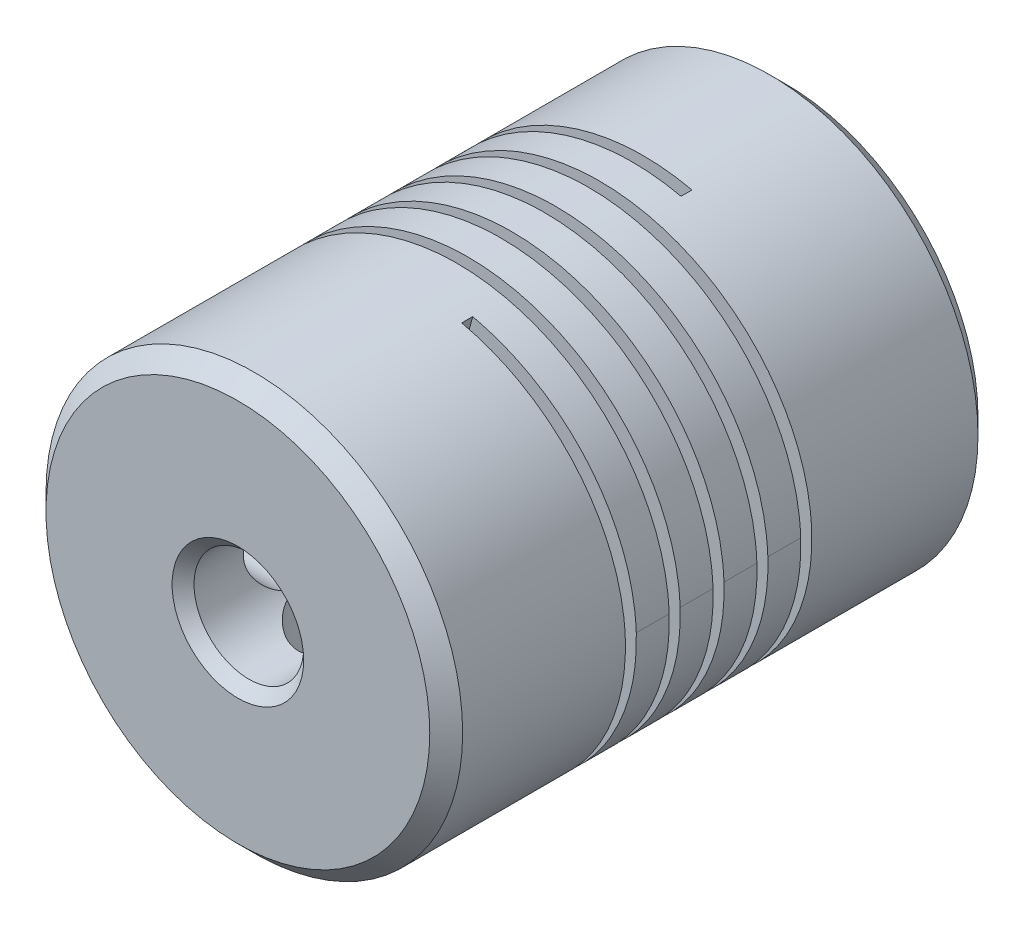
SolidWorks part; units mm, degrees
material "6063-T5"
ref_plane "Спереди" through (0, 0, 0) normal (0, 0, 1) x (1, 0, 0)
ref_plane "Сверху" through (0, 0, 0) normal (0, 1, 0) x (1, 0, 0)
ref_plane "Справа" through (0, 0, 0) normal (1, 0, 0) x (0, 0, -1)
sketch "Эскиз1" plane through (0, 0, 0) normal (0, 0, 1) x (1, 0, 0)
  circle A0 centre (0, 0) radius 9.5
  dimension "D1" = 19
extrude "Body" add sketch "Эскиз1" along normal blind 25
sketch "Эскиз2" plane through (0, 0, 25) normal (0, 0, 1) x (1, 0, 0)
  circle A0 centre (0, 0) radius 2.5
  dimension "D1" = 5
extrude "RodHole" cut sketch "Эскиз2" against normal blind 42
chamfer "Фаска1" distance 0.75 angle 45 2 edges at (9.5, 0, 25) (9.5, 0, 0)
chamfer "Фаска2" distance 0.5 angle 45 2 edges at (2.5, 0, 25) (2.5, 0, 0)
sketch "Эскиз3" plane through (0, 0, 0) normal (1, 0, 0) x (0, 0, -1)
  circle A0 centre (-4.5, 0) radius 1.75
  circle A1 centre (-20.5, 0) radius 1.75
  dimension "D1" = 3.5
  dimension "D2" = 3.5
  dimension "D3" = 4.5
  dimension "D4" = 20.5
extrude "SetScrewHoles1" cut sketch "Эскиз3" against normal blind 12
cosmetic thread "Условное изображение резьбы1" parameters "D2"=4
cosmetic thread "Условное изображение резьбы2" parameters "D2"=4
sketch "Эскиз4" plane through (0, 0, 0) normal (0, 1, 0) x (1, 0, 0)
  circle A0 centre (0, -4.5) radius 1.75
  circle A1 centre (0, -20.5) radius 1.75
  dimension "D1" = 3.5
  dimension "D2" = 3.5
  dimension "D3" = 4.5
  dimension "D4" = 20.5
extrude "SetScrewHoles2" cut sketch "Эскиз4" against normal blind 12
cosmetic thread "Условное изображение резьбы3" parameters "D2"=4
cosmetic thread "Условное изображение резьбы4" parameters "D2"=4
ref_plane "Плоскость1" through (0, 0, 17) normal (0, 0, 1) x (1, 0, 0)
sketch "Эскиз6" plane through (0, 0, 17) normal (0, 0, 1) x (1, 0, 0)
  circle A0 centre (0, 0) radius 9.5
curve "Спираль1" pitch 2 height 10 radius 9.5 centre (0, 0, 17) axis (0, 0, -1) start towards (0.2588, 0.9659, 0)
ref_plane "Плоскость2" through (0, 0, 0) normal (0.9659, -0.2588, 0) x (0, 0, -1)
sketch "Эскиз7" plane through (0, 0, 0) normal (0.9659, -0.2588, 0) x (0, 0, -1)
  line L0 (-0.75, 9.5) -> (-24.25, 9.5) construction
  line L1 (-6.75, 10.0798) -> (-7.25, 10.0798)
  line L2 (-6.75, 10.0798) -> (-6.75, 1.4319)
  line L3 (-6.75, 1.4319) -> (-7.25, 1.4319)
  line L4 (-7.25, 10.0798) -> (-7.25, 1.4319)
  spline S0 degree 3 poles (-17, 9.5) (-16.9586, 9.5) (-16.8749, 9.0054) (-16.75, 6.8924) (-16.625, 3.7301) (-16.5, 0) (-16.375, -3.7301) (-16.25, -6.8924) (-16.125, -9.0054) (-16, -9.7473) (-15.875, -9.0054) (-15.75, -6.8924) (-15.625, -3.7301) (-15.5, 0) (-15.375, 3.7301) (-15.25, 6.8924) (-15.125, 9.0054) (-15, 9.7473) (-14.875, 9.0054) (-14.75, 6.8924) (-14.625, 3.7301) (-14.5, 0) (-14.375, -3.7301) (-14.25, -6.8924) (-14.125, -9.0054) (-14, -9.7473) (-13.875, -9.0054) (-13.75, -6.8924) (-13.625, -3.7301) (-13.5, 0) (-13.375, 3.7301) (-13.25, 6.8924) (-13.125, 9.0054) (-13, 9.7473) (-12.875, 9.0054) (-12.75, 6.8924) (-12.625, 3.7301) (-12.5, 0) (-12.375, -3.7301) (-12.25, -6.8924) (-12.125, -9.0054) (-12, -9.7473) (-11.875, -9.0054) (-11.75, -6.8924) (-11.625, -3.7301) (-11.5, 0) (-11.375, 3.7301) (-11.25, 6.8924) (-11.125, 9.0054) (-11, 9.7473) (-10.875, 9.0054) (-10.75, 6.8924) (-10.625, 3.7301) (-10.5, 0) (-10.375, -3.7301) (-10.25, -6.8924) (-10.125, -9.0054) (-10, -9.7473) (-9.875, -9.0054) (-9.75, -6.8924) (-9.625, -3.7301) (-9.5, 0) (-9.375, 3.7301) (-9.25, 6.8924) (-9.125, 9.0054) (-9, 9.7473) (-8.875, 9.0054) (-8.75, 6.8924) (-8.625, 3.7301) (-8.5, 0) (-8.375, -3.7301) (-8.25, -6.8924) (-8.125, -9.0054) (-8, -9.7473) (-7.875, -9.0054) (-7.75, -6.8924) (-7.625, -3.7301) (-7.5, 0) (-7.375, 3.7301) (-7.25, 6.8924) (-7.1251, 9.0054) (-7.0414, 9.5) (-7, 9.5) knots 0 0 0 0 0.0125 0.025 0.0375 0.05 0.0625 0.075 0.0875 0.1 0.1125 0.125 0.1375 0.15 0.1625 0.175 0.1875 0.2 0.2125 0.225 0.2375 0.25 0.2625 0.275 0.2875 0.3 0.3125 0.325 0.3375 0.35 0.3625 0.375 0.3875 0.4 0.4125 0.425 0.4375 0.45 0.4625 0.475 0.4875 0.5 0.5125 0.525 0.5375 0.55 0.5625 0.575 0.5875 0.6 0.6125 0.625 0.6375 0.65 0.6625 0.675 0.6875 0.7 0.7125 0.725 0.7375 0.75 0.7625 0.775 0.7875 0.8 0.8125 0.825 0.8375 0.85 0.8625 0.875 0.8875 0.9 0.9125 0.925 0.9375 0.95 0.9625 0.975 0.9875 1 1 1 1 construction
  point P0 (-7, 9.5)
  dimension "D1" = 0.5
  dimension "D2" = 0.25
sweep "Вырез-По траектории1" cut profiles "Эскиз7" path "Спираль1" align with end faces yes
